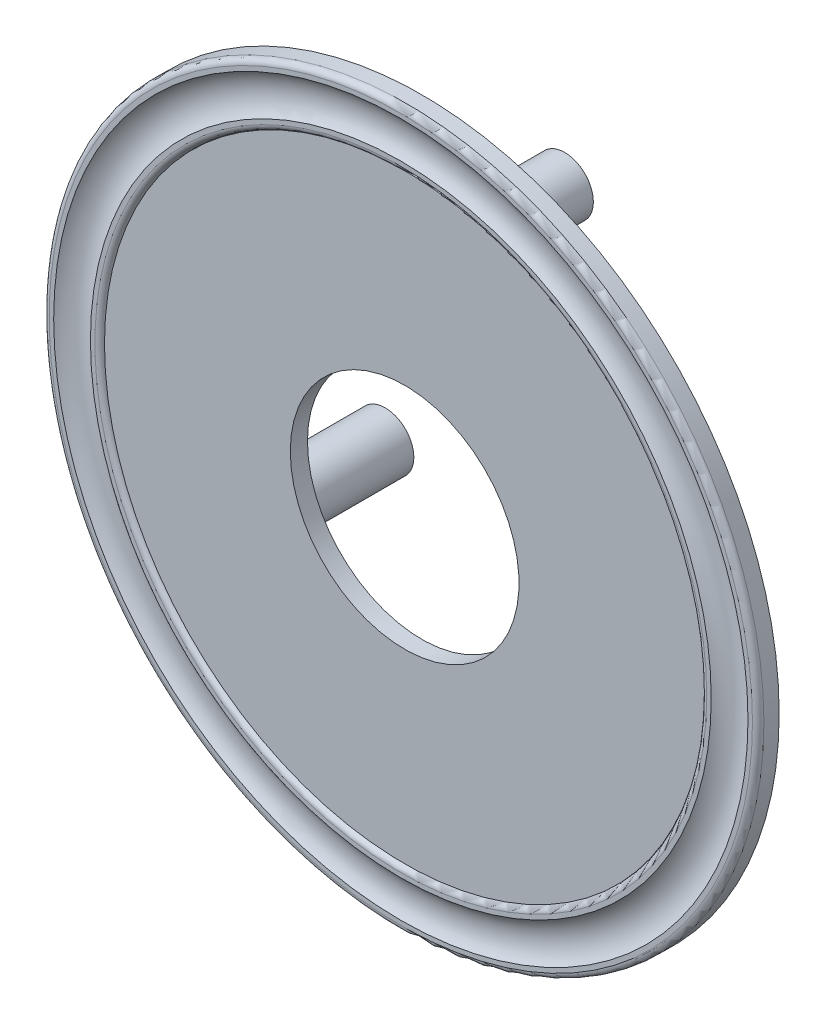
SolidWorks part; units mm, degrees
ref_plane "前基準面" through (0, 0, 0) normal (0, 0, 1) x (1, 0, 0)
ref_plane "上基準面" through (0, 0, 0) normal (0, 1, 0) x (1, 0, 0)
ref_plane "右基準面" through (0, 0, 0) normal (1, 0, 0) x (0, 0, -1)
ref_axis "基準軸1" through (0, -55, 0) along (0, 1, 0)
ref_axis "基準軸2" through (-88.99, 0, 0) along (1, 0, 0)
ref_axis "基準軸3" through (0, 0, 55) along (0, 0, -1)
sketch "草圖3" plane through (0, 0, 0) normal (0, 1, 0) x (1, 0, 0)
  line L1 (-10, 15) -> (10, 15)
  line L2 (0, -55) -> (0, 55) construction
  line L3 (-10, 15) -> (-10, 9.6604)
  line L4 (-8, 7.6604) -> (-6.4279, 7.6604)
  line L5 (10, 15) -> (10, 9.6604)
  line L6 (8, 7.6604) -> (6.4279, 7.6604)
  line L7 (-55, 0) -> (55, 0) construction
  arc A0 (6.4279, 7.6604) -> (-6.4279, 7.6604) centre (0, 0) ccw
  arc A1 (-10, 9.6604) -> (-8, 7.6604) centre (-8, 9.6604) ccw
  arc A2 (10, 9.6604) -> (8, 7.6604) centre (8, 9.6604) cw
  point P8 (0, 15)
  dimension "D2" = 10
  dimension "D5" = 2
  dimension "D6" = 2
  dimension "D1" = 80
  dimension "D3" = 20
  dimension "D4" = 15
  dimension "D7" = 7.3396
ref_plane "平面1" through (115, 0, 0) normal (1, 0, 0) x (0, 0, -1)
ref_axis "基準軸7" through (115, 0, 57.074) along (0, 0, -1)
revolve "旋轉2" add sketch "草圖3" angle 360 about axis through (115, 0, 57.074) along (0, 0, -1)
sketch "草圖7" plane through (0, 0, -15) normal (0, 0, -1) x (-1, 0, 0)
  line L0 (-115, 0) -> (-115, 133.8375) construction
  line L1 (-115, 0) -> (0.9066, -66.9187) construction
  line L2 (-115, 0) -> (-230.9066, -66.9187) construction
  circle A0 centre (-115, 0) radius 105 construction
  circle A1 centre (-115, 0) radius 105
  circle A2 centre (-115, 0) radius 40
  point P9 (-115, 0)
  point P18 (-115, 0)
  dimension "D1" = 80
  dimension "D3" = 65
  dimension "D2" = 3
extrude "填料-伸長1" add sketch "草圖7" against normal blind 6
sketch "草圖8" plane through (0, 0, -15) normal (0, 0, -1) x (-1, 0, 0)
  line L0 (-115, 0) -> (-115, 72.5) construction
  line L1 (-115, 0) -> (-177.7868, -36.25) construction
  line L2 (-115, 0) -> (-52.2132, -36.25) construction
  circle A0 centre (-115, 0) radius 72.5 construction
  circle A1 centre (-115, 72.5) radius 10
  circle A2 centre (-52.2132, -36.25) radius 10
  circle A3 centre (-177.7868, -36.25) radius 10
  circle A4 centre (-115, 0) radius 40 construction
  circle A5 centre (-115, 0) radius 40 construction
  dimension "D3" = 32.5
  dimension "D4" = 20
  dimension "D1" = 120
  dimension "D2" = 120
extrude "填料-伸長2" add sketch "草圖8" along normal blind 50
